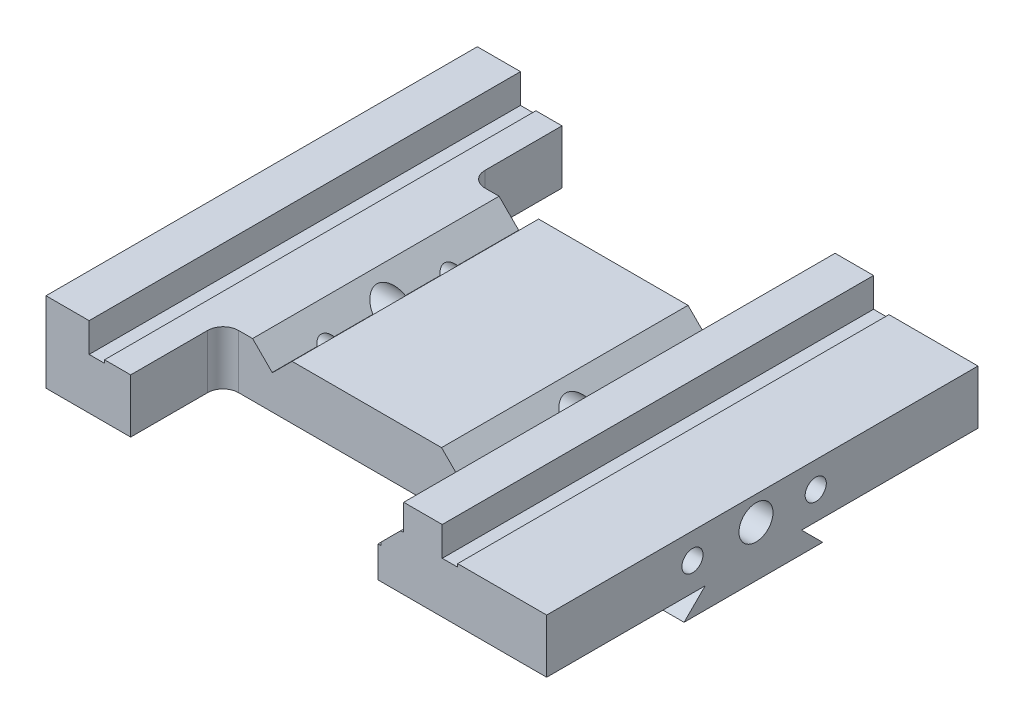
SolidWorks part; units mm, degrees
ref_plane "Front Plane" through (0, 0, 0) normal (0, 0, 1) x (1, 0, 0)
ref_plane "Top Plane" through (0, 0, 0) normal (0, 1, 0) x (1, 0, 0)
ref_plane "Right Plane" through (0, 0, 0) normal (1, 0, 0) x (0, 0, -1)
sketch "Sketch1" plane through (0, 0, 0) normal (0, 0, 1) x (1, 0, 0)
  line L1 (-148.8234, 14.864) -> (-134.8234, 14.864)
  line L2 (-134.8234, 14.864) -> (-134.8234, 6.364)
  line L3 (-129.8234, 6.364) -> (-111.7719, 6.364)
  line L4 (-111.7719, 6.364) -> (-105.4079, 0)
  line L5 (-105.4079, 0) -> (-105.3079, 0)
  line L6 (-105.3079, 0) -> (-98.944, 6.364)
  line L7 (-98.944, 6.364) -> (-50.444, 6.364)
  line L8 (-50.444, 6.364) -> (-44.08, 0)
  line L10 (-40.08, 0) -> (-33.7161, 6.364)
  line L11 (-33.7161, 6.364) -> (-32.7161, 6.364)
  line L12 (-32.7161, 6.364) -> (-32.7161, 14.864)
  line L13 (-32.7161, 14.864) -> (-20.2161, 14.864)
  line L15 (-15.2161, 6.364) -> (13.6766, 6.364)
  line L16 (13.6766, 6.364) -> (13.6766, -11.136)
  line L17 (13.6766, -11.136) -> (-148.8234, -11.136)
  line L19 (-134.8234, 6.364) -> (-134.8234, 5.364)
  line L20 (-134.8234, 5.364) -> (-129.8234, 5.364)
  line L21 (-129.8234, 5.364) -> (-129.8234, 6.364)
  line L22 (-40.08, 0) -> (-40.08, -1)
  line L23 (-40.08, -1) -> (-44.08, -1)
  line L24 (-44.08, -1) -> (-44.08, 0)
  line L25 (-15.2161, 6.364) -> (-15.2161, 5.364)
  line L26 (-15.2161, 5.364) -> (-20.2161, 5.364)
  line L28 (-20.2161, 5.364) -> (-20.2161, 14.864)
  line L29 (-148.8234, 14.864) -> (-148.8234, -11.136)
  point P0 (-20.2366, 14.6916)
  dimension "D1" = 162.5
  dimension "D2" = 9
  dimension "D3" = 9
  dimension "D4" = 0.1
  dimension "D5" = 9
  dimension "D6" = 9
  dimension "D7" = 4
  dimension "D8" = 12.5
  dimension "D9" = 48.5
  dimension "D10" = 1
  dimension "D11" = 14
  dimension "D12" = 225
  dimension "D13" = 17.5
  dimension "D15" = 90
  dimension "D16" = 1
  dimension "D17" = 5
  dimension "D18" = 1
  dimension "D19" = 1
  dimension "D21" = 5
  dimension "D22" = 1
  dimension "D24" = 26
  dimension "D25" = 1
extrude "Boss-Extrude1" add sketch "Sketch1" along normal blind 140
sketch "Sketch2" plane through (13.6766, 0, 0) normal (1, 0, 0) x (0, 0, -1)
  line L0 (-88.5445, -11.136) -> (-95.3948, -17.9863)
  line L1 (-140, -11.136) -> (0, -11.136) construction
  line L2 (-95.3948, -17.9863) -> (-50.4097, -17.9863)
  line L3 (-50.4097, -17.9863) -> (-57.26, -11.136)
  line L4 (-57.26, -11.136) -> (-88.5445, -11.136)
  dimension "D1" = 45
  dimension "D2" = 45
extrude "Boss-Extrude2" add sketch "Sketch2" against normal blind 162.5
sketch "Sketch3" plane through (0, -11.136, 0) normal (0, -1, 0) x (1, 0, 0)
  line L0 (-148.8234, 0) -> (13.6766, 0) construction
  line L1 (-121.3429, 0) -> (-41.0392, 0)
  line L2 (-121.3429, 0) -> (-121.3429, 25)
  line L3 (-116.3429, 30) -> (-46.0392, 30)
  line L4 (-41.0392, 0) -> (-41.0392, 25)
  line L5 (-148.8234, 140) -> (13.6766, 140) construction
  line L6 (-121.3429, 140) -> (-41.0392, 140)
  line L7 (-121.3429, 140) -> (-121.3429, 115)
  line L8 (-116.3429, 110) -> (-46.0392, 110)
  line L9 (-41.0392, 140) -> (-41.0392, 115)
  line L10 (-148.8234, 140) -> (13.6766, 140) construction
  arc A0 (-46.0392, 30) -> (-41.0392, 25) centre (-46.0392, 25) cw
  arc A1 (-121.3429, 25) -> (-116.3429, 30) centre (-116.3429, 25) cw
  arc A2 (-46.0392, 110) -> (-41.0392, 115) centre (-46.0392, 115) ccw
  arc A3 (-121.3429, 115) -> (-116.3429, 110) centre (-116.3429, 115) ccw
  dimension "D1" = 5
  dimension "D2" = 30
  dimension "D3" = 30
extrude "Cut-Extrude1" cut sketch "Sketch3" against normal blind 100
sketch "Sketch4" plane through (13.6766, 0, 0) normal (1, 0, 0) x (0, 0, -1)
  circle A0 centre (-72.0525, -1.5555) radius 5.5191
extrude "Cut-Extrude2" cut sketch "Sketch4" against normal blind 1000
sketch "Sketch5" plane through (13.6766, 0, 0) normal (1, 0, 0) x (0, 0, -1)
  circle A0 centre (-92.6666, -2.0017) radius 3.4284
  circle A2 centre (-52.6666, -2.0017) radius 3.4284
  dimension "D1" = 2
extrude "Cut-Extrude3" cut sketch "Sketch5" against normal blind 1000
